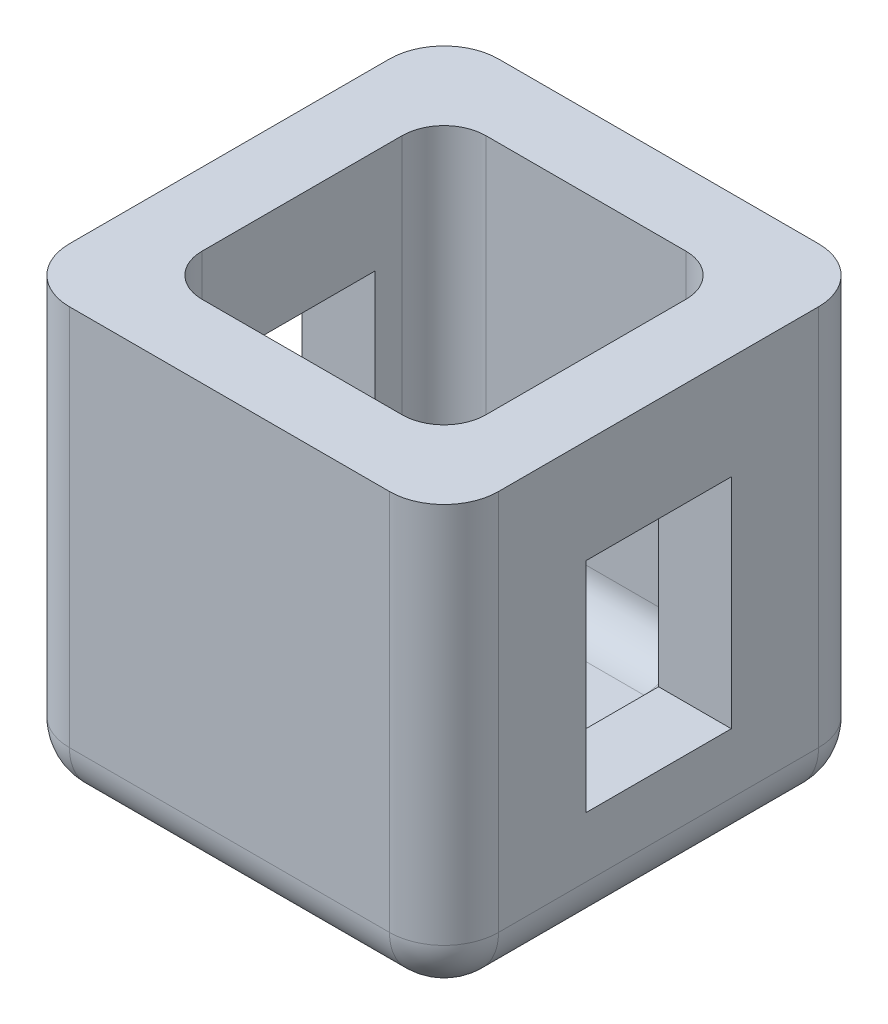
SolidWorks part; units mm, degrees
ref_plane "Front Plane" through (0, 0, 0) normal (0, 0, 1) x (1, 0, 0)
ref_plane "Top Plane" through (0, 0, 0) normal (0, 1, 0) x (1, 0, 0)
ref_plane "Right Plane" through (0, 0, 0) normal (1, 0, 0) x (0, 0, -1)
sketch "Sketch1" plane through (0, 0, 0) normal (0, 1, 0) x (1, 0, 0)
  line L1 (-115.4685, 69.6703) -> (120.5315, 69.6703)
  line L2 (-115.4685, 69.6703) -> (-115.4685, -166.3297)
  line L3 (-115.4685, -166.3297) -> (120.5315, -166.3297)
  line L4 (120.5315, 69.6703) -> (120.5315, -166.3297)
  dimension "D1" = 236
  dimension "D2" = 236
extrude "Boss-Extrude1" add sketch "Sketch1" along normal blind 240
shell "Shell1" thickness 40 removed face at (2.5315, 240, 48.3297)
fillet "Fillet1" radius 23 8 edges at (2.5315, 40, -29.6703) (80.5315, 40, 48.3297) (2.5315, 40, 126.3297) (-75.4685, 40, 48.3297) (80.5315, 140, -29.6703) (80.5315, 140, 126.3297) (-75.4685, 140, 126.3297) (-75.4685, 140, -29.6703)
fillet "Fillet2" radius 30 8 edges at (2.5315, 0, 166.3297) (120.5315, 0, 48.3297) (2.5315, 0, -69.6703) (-115.4685, 0, 48.3297) (-115.4685, 120, -69.6703) (120.5315, 120, -69.6703) (-115.4685, 120, 166.3297) (120.5315, 120, 166.3297)
sketch "Sketch3" plane through (120.5315, 0, 0) normal (1, 0, 0) x (0, 0, -1)
  line L0 (-166.3297, 0) -> (69.6703, 0) construction
  line L1 (-88.3297, 183) -> (-8.3297, 183)
  line L2 (-88.3297, 183) -> (-88.3297, 63)
  line L3 (-88.3297, 63) -> (-8.3297, 63)
  line L4 (-8.3297, 183) -> (-8.3297, 63)
  line L5 (69.6703, 240) -> (69.6703, 0) construction
  dimension "D1" = 63
  dimension "D2" = 80
  dimension "D3" = 120
  dimension "D4" = 78
extrude "Cut-Extrude2" cut sketch "Sketch3" against normal blind 240
